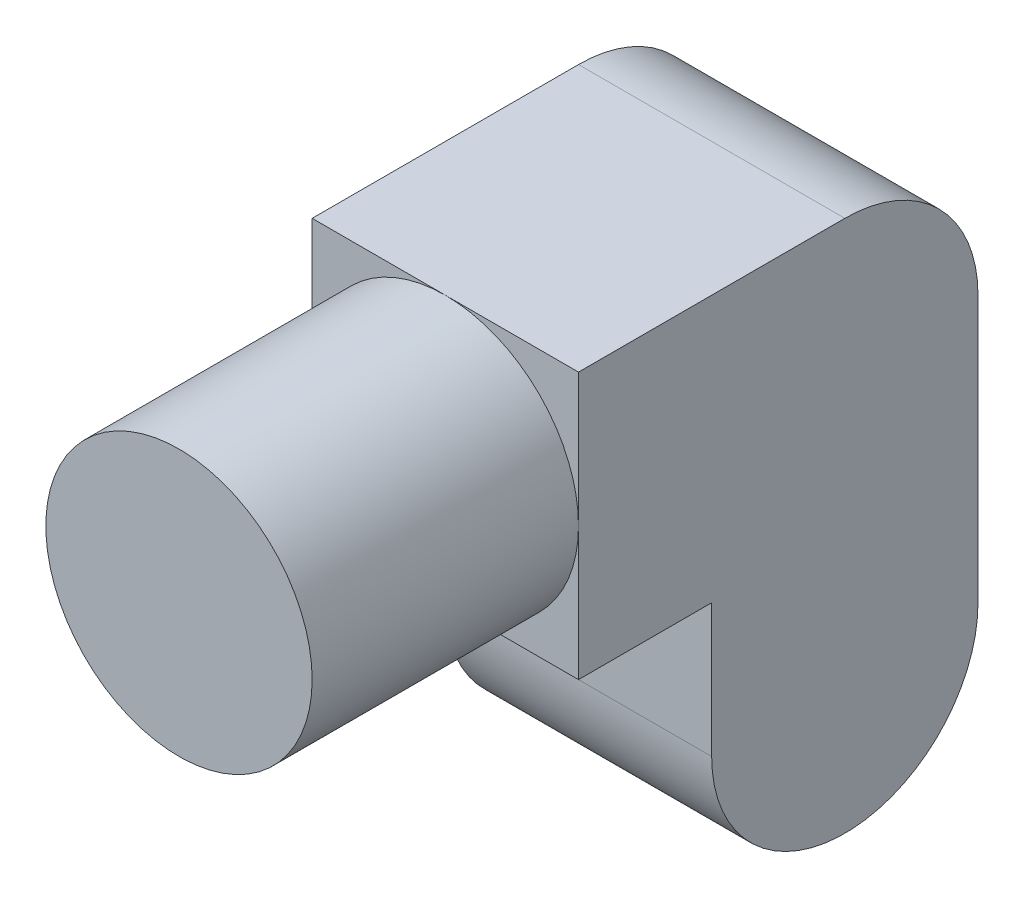
SolidWorks part; units mm, degrees
ref_plane "Front Plane" through (0, 0, 0) normal (0, 0, 1) x (1, 0, 0)
ref_plane "Top Plane" through (0, 0, 0) normal (0, 1, 0) x (1, 0, 0)
ref_plane "Right Plane" through (0, 0, 0) normal (1, 0, 0) x (0, 0, -1)
sketch "Sketch2" plane through (0, 0, 0) normal (1, 0, 0) x (0, 0, -1)
  line L1 (-80, -40) -> (0, -40)
  line L2 (-80, -40) -> (-80, 40)
  line L3 (-80, 40) -> (40, 40)
  line L4 (80, -40) -> (80, 0)
  line L5 (-80, -40) -> (64, 32) construction
  line L6 (-80, 40) -> (80, -40) construction
  line L8 (80, -40) -> (80, -80)
  line L10 (0, -40) -> (0, -80)
  arc A0 (0, -80) -> (80, -80) centre (40, -80) ccw
  arc A1 (80, 0) -> (40, 40) centre (40, 0) ccw
  point P0 (0, 0)
  dimension "D1" = 80
extrude "Boss-Extrude1" add sketch "Sketch2" along normal blind 80
sketch "Sketch3" plane through (0, 0, 80) normal (0, 0, 1) x (1, 0, 0)
  circle A0 centre (40, 0) radius 40
extrude "Boss-Extrude2" add sketch "Sketch3" along normal blind 40
sketch "Sketch5" plane through (0, 0, 80) normal (0, 0, 1) x (1, 0, 0)
  line L1 (0, 40) -> (80, 40)
  line L2 (0, 40) -> (0, -40)
  line L3 (0, -40) -> (80, -40)
  line L4 (80, 40) -> (80, -40)
  circle A0 centre (40, 0) radius 40
  arc M1 (40, 40) -> (80, 0) centre (40, 0) cw
  line M2 (80, 0) -> (80, 40)
  line M3 (80, 40) -> (40, 40)
extrude "Cut-Extrude3" cut sketch "Sketch5" against normal blind 40 contours M3 M1 M2 | A0 L1 L2 | A0 L2 L3 | A0 L3 L4 region at (8.9347, 31.0653, 80) region at (71.0653, 31.0653, 80) region at (8.9347, -31.0653, 80) region at (71.0653, -31.0653, 80)
